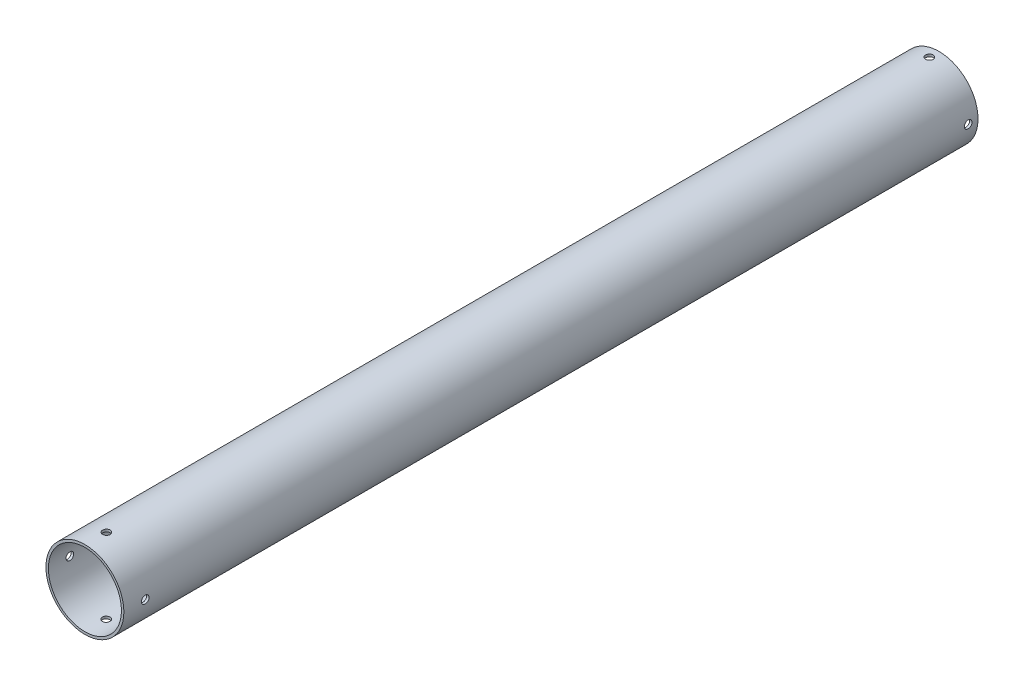
SolidWorks part; units mm, degrees
material "PC High Viscosity"
ref_plane "Front Plane" through (0, 0, 0) normal (0, 0, 1) x (1, 0, 0)
ref_plane "Top Plane" through (0, 0, 0) normal (0, 1, 0) x (1, 0, 0)
ref_plane "Right Plane" through (0, 0, 0) normal (1, 0, 0) x (0, 0, -1)
sketch "Sketch1" plane through (0, 0, 0) normal (0, 0, 1) x (1, 0, 0)
  circle A0 centre (0, 0) radius 23.8125
  circle A1 centre (0, 0) radius 25.4
  dimension "D1" = 50.8
  dimension "D2" = 47.625
extrude "Boss-Extrude1" add sketch "Sketch1" along normal mid plane 556.685
sketch "Sketch2" plane through (0, 0, 0) normal (1, 0, 0) x (0, 0, -1)
  line L0 (278.3425, -25.4) -> (278.3425, 25.4) construction
  circle A1 centre (271.9925, 0) radius 2.4892
  dimension "D1" = 4.9784
  dimension "D2" = 6.35
extrude "Cut-Extrude1" cut sketch "Sketch2" against normal through all both and the other way through all
sketch "Sketch3" plane through (0, 0, 0) normal (0, 1, 0) x (1, 0, 0)
  line L0 (25.4, 278.3425) -> (-25.4, 278.3425) construction
  circle A0 centre (0, 271.9925) radius 2.4892
  dimension "D1" = 4.9784
  dimension "D2" = 6.35
extrude "Cut-Extrude2" cut sketch "Sketch3" against normal through all both and the other way through all
sketch "Sketch4" plane through (0, 0, 0) normal (1, 0, 0) x (0, 0, -1)
  line L0 (-278.3425, 25.4) -> (-278.3425, -25.4) construction
  circle A0 centre (-264.3725, 0) radius 2.4892
  dimension "D1" = 13.97
  dimension "D2" = 4.9784
extrude "Cut-Extrude3" cut sketch "Sketch4" against normal through all both and the other way through all contours A0
sketch "Sketch5" plane through (0, 0, 0) normal (0, 1, 0) x (1, 0, 0)
  line L0 (-25.4, -278.3425) -> (25.4, -278.3425) construction
  circle A0 centre (0, -264.3725) radius 2.4892
  dimension "D1" = 4.9784
  dimension "D2" = 13.97
extrude "Cut-Extrude4" cut sketch "Sketch5" against normal through all both and the other way through all
equation "\"D1@Boss-Extrude1\"=21.125in+3.625mm"
